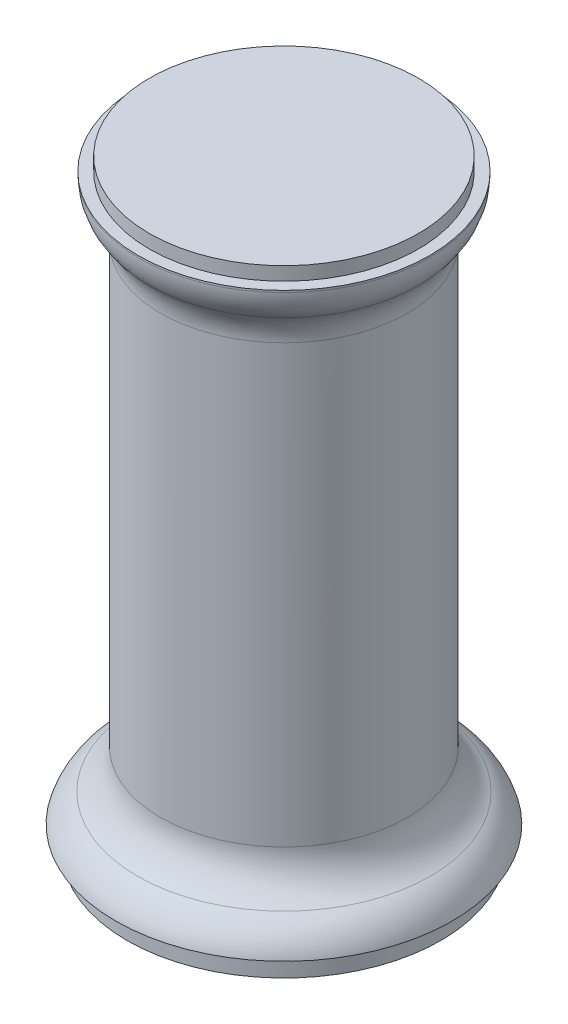
SolidWorks part; units mm, degrees
material "1060 Alloy"
ref_plane "Front Plane" through (0, 0, 0) normal (0, 0, 1) x (1, 0, 0)
ref_plane "Top Plane" through (0, 0, 0) normal (0, 1, 0) x (1, 0, 0)
ref_plane "Right Plane" through (0, 0, 0) normal (1, 0, 0) x (0, 0, -1)
sketch "Sketch1" plane through (0, 0, 0) normal (0, 1, 0) x (1, 0, 0)
  circle A0 centre (0, 0) radius 35
  dimension "D1" = 70
extrude "Boss-Extrude1" add sketch "Sketch1" along normal blind 5
sketch "Sketch3" plane through (0, 5, 0) normal (0, 1, 0) x (1, 0, 0)
  circle A0 centre (0, 0) radius 37.5
  dimension "D1" = 75
extrude "Boss-Extrude2" add sketch "Sketch3" along normal blind 5
sketch "Sketch4" plane through (0, 10, 0) normal (0, 1, 0) x (1, 0, 0)
  circle A0 centre (0, 0) radius 27.5
  dimension "D1" = 55
extrude "Boss-Extrude5" add sketch "Sketch4" along normal blind 116 contours A0
sketch "Sketch5" plane through (0, 126, 0) normal (0, 1, 0) x (1, 0, 0)
  circle A0 centre (0, 0) radius 32.5
  dimension "D1" = 65
extrude "Boss-Extrude6" add sketch "Sketch5" along normal blind 5 contours A0
sketch "Sketch6" plane through (0, 131, 0) normal (0, 1, 0) x (1, 0, 0)
  circle A0 centre (0, 0) radius 30
  dimension "D1" = 60
extrude "Boss-Extrude7" add sketch "Sketch6" along normal blind 3
fillet "Fillet1" radius 10 2 edges at (0, 10, 27.5) (0, 126, 27.5)
fillet "Fillet2" radius 10 2 edges at (0, 126, 32.5) (0, 10, 37.5)
